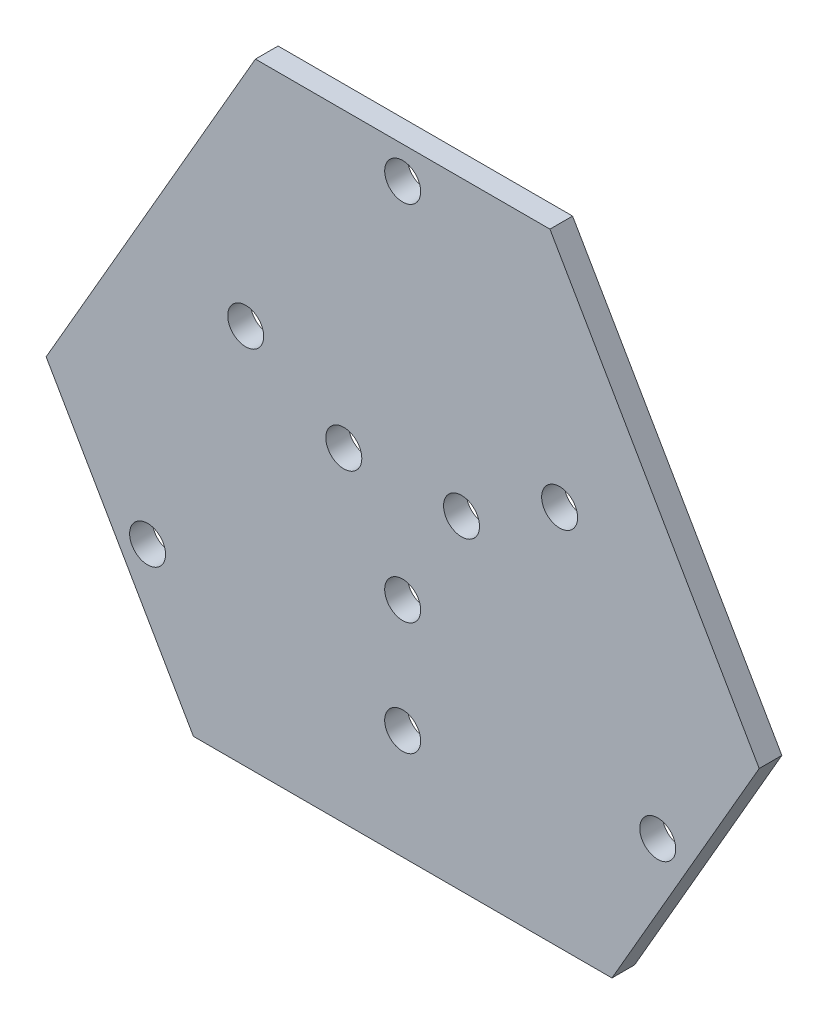
SolidWorks part; units mm, degrees
material "6061-T6 (SS)"
ref_plane "Front" through (0, 0, 0) normal (0, 0, 1) x (1, 0, 0)
ref_plane "Top" through (0, 0, 0) normal (0, 1, 0) x (1, 0, 0)
ref_plane "Right" through (0, 0, 0) normal (1, 0, 0) x (0, 0, -1)
sketch "Sketch1" plane through (0, 0, 0) normal (0, 0, 1) x (1, 0, 0)
  line L0 (-41.275, 91.5635) -> (41.275, 91.5635)
  line L1 (-99.9338, -10.0365) -> (0, 0) construction
  line L2 (-41.275, 91.5635) -> (0, 0) construction
  line L3 (41.275, 91.5635) -> (99.9338, -10.0365)
  line L4 (99.9338, -10.0365) -> (-99.9338, -10.0365) construction
  line L5 (99.9338, -10.0365) -> (58.6588, -81.5269)
  line L6 (58.6588, -81.5269) -> (-58.6588, -81.5269)
  line L7 (-58.6588, -81.5269) -> (-99.9338, -10.0365)
  line L8 (-99.9338, -10.0365) -> (-41.275, 91.5635)
  line L9 (0, 0) -> (41.275, 91.5635) construction
  line L10 (0, 0) -> (99.9338, -10.0365) construction
  line L11 (0, 0) -> (58.6588, -81.5269) construction
  line L13 (0, 0) -> (-58.6588, -81.5269) construction
  dimension "D1" = 82.55
  dimension "D2" = 101.6
extrude "Boss-Extrude1" add sketch "Sketch1" along normal blind 6.35
ref_axis "Axis1" through (0, 0, 0) along (0, 0, 1)
sketch "Sketch2" plane through (0, 0, 6.35) normal (0, 0, 1) x (1, 0, 0)
  line L0 (0, 0) -> (0, 82.55) construction
  line L1 (0, 0) -> (16.4978, 9.525) construction
  line L2 (16.4978, 9.525) -> (43.9941, 25.4) construction
  line L3 (43.9941, 25.4) -> (70.6044, 40.7635) construction
  line L4 (99.9338, -10.0365) -> (41.275, 91.5635) construction
  dimension "D1" = 82.55
  dimension "D2" = 19.05
  dimension "D3" = 31.75
hole_wizard "3/8 Clearance Hole1" positions "Sketch4" profile "Sketch3" hole size "3/8" standard "ANSI Inch" end condition through all
sketch "Sketch4" plane through (0, 0, 6.35) normal (0, 0, 1) x (1, 0, 0)
  point P0 (0, 82.55)
sketch "Sketch3" plane through (0, 82.55, 6.35) normal (1, 0, 0) x (0, -1, 0)
  line L0 (0, 0) -> (0, 6.35)
  line L1 (0, 6.35) -> (5.0419, 6.35)
  line L2 (5.0419, 6.35) -> (5.0419, 0)
  line L5 (5.0419, 0) -> (0, 0)
  line L11 (0, -6.35) -> (0, 107.95) construction
  dimension "Thru Hole Dia." = 10.0838
  dimension "Thru Hole Depth" = 6.35
hole_wizard "3/8 Clearance Hole2" positions "Sketch7" profile "Sketch6" hole size "3/8" standard "ANSI Inch" end condition through all
sketch "Sketch7" plane through (0, 0, 6.35) normal (0, 0, 1) x (1, 0, 0)
  point P0 (43.9941, 25.4)
  point P3 (16.4978, 9.525)
sketch "Sketch6" plane through (43.9941, 25.4, 6.35) normal (1, 0, 0) x (0, -1, 0)
  line L0 (0, 0) -> (0, 6.35)
  line L1 (0, 6.35) -> (5.0419, 6.35)
  line L2 (5.0419, 6.35) -> (5.0419, 0)
  line L5 (5.0419, 0) -> (0, 0)
  line L11 (0, -6.35) -> (0, 107.95) construction
  dimension "Thru Hole Dia." = 10.0838
  dimension "Thru Hole Depth" = 6.35
pattern_circular "CirPattern1" count 3 over 360 about axis through (0, 0, 0) along (0, 0, 1) of "3/8 Clearance Hole1", "3/8 Clearance Hole2"
